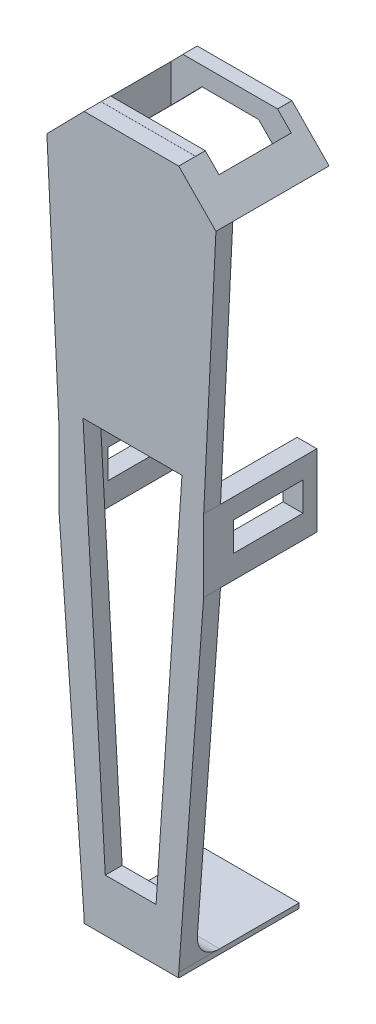
SolidWorks part; units mm, degrees
material "PLA"
ref_plane "Front Plane" through (0, 0, 0) normal (0, 0, 1) x (1, 0, 0)
ref_plane "Top Plane" through (0, 0, 0) normal (0, 1, 0) x (1, 0, 0)
ref_plane "Right Plane" through (0, 0, 0) normal (1, 0, 0) x (0, 0, -1)
sketch "Sketch1" plane through (0, 0, 0) normal (0, 0, 1) x (1, 0, 0)
  line L0 (-37.3414, 34.6091) -> (22.6586, 34.6091)
  line L1 (22.6586, 34.6091) -> (50.9429, 6.3248)
  line L2 (50.9429, 6.3248) -> (50.9429, -53.6752)
  line L3 (50.9429, -53.6752) -> (22.6586, -81.9594)
  line L4 (22.6586, -81.9594) -> (-37.3414, -81.9594)
  line L5 (-37.3414, -81.9594) -> (-64.6578, -54.643)
  line L6 (-64.6578, -54.643) -> (-64.6578, 5.357)
  line L7 (-64.6578, 5.357) -> (-37.3414, 34.6091)
  line L8 (-27.6371, 26.0388) -> (-43.235, 10.1409)
  line L13 (-8.1397, -94.0869) -> (21.8603, -94.0869)
  line L15 (-27.6371, 26.0388) -> (-19.7574, 18.3077)
  line L16 (-43.235, 10.1409) -> (-35.3553, 2.4098)
  line L17 (-19.7574, 18.3077) -> (-35.3553, 2.4098)
  line L18 (-8.1397, 25.9131) -> (-8.1397, 18.1821)
  line L19 (-27.7871, 25.9131) -> (11.5077, 25.9131)
  line L20 (-27.7871, 25.9131) -> (-27.7871, 18.1821)
  line L21 (-27.7871, 18.1821) -> (11.5077, 18.1821)
  line L22 (11.5077, 25.9131) -> (11.5077, 18.1821)
  line L23 (-8.1397, 18.1821) -> (-8.1397, 25.9131) construction
  line L24 (-27.7871, 22.0476) -> (11.5077, 22.0476) construction
  line L25 (26.9557, 10.1409) -> (19.0759, 2.4098)
  line L26 (3.478, 18.3077) -> (19.0759, 2.4098)
  line L27 (11.3577, 26.0388) -> (3.478, 18.3077)
  line L28 (11.3577, 26.0388) -> (26.9557, 10.1409)
  line L29 (21.8603, -94.0869) -> (-38.1397, -94.0869)
  line L30 (21.8603, -94.0869) -> (21.8603, -124.0869)
  line L31 (21.8603, -124.0869) -> (-38.1397, -124.0869)
  line L32 (-38.1397, -94.0869) -> (-38.1397, -124.0869)
  line L33 (-30.3382, -94.0869) -> (13.6618, -94.0869)
  line L34 (-30.3382, -94.0869) -> (-30.3382, -124.0869)
  line L35 (-30.3382, -124.0869) -> (13.6618, -124.0869)
  line L36 (13.6618, -94.0869) -> (13.6618, -124.0869)
  line L37 (-8.3382, -124.0869) -> (-8.3382, -94.0869) construction
  line L38 (-30.3382, -109.0869) -> (13.6618, -109.0869) construction
  point P12 (-8.1397, 22.0476)
  point P17 (-8.3382, -109.0869)
  dimension "D1" = 135
  dimension "D2" = 135
  dimension "D3" = 40
  dimension "D4" = 135
  dimension "D5" = 120
  dimension "D6" = 30
  dimension "D7" = 22.2719
  dimension "D8" = 11.039
  dimension "D9" = 7.7311
  dimension "D10" = 39.2948
  dimension "D11" = 60
  dimension "D12" = 30
  dimension "D13" = 44
extrude "Boss-Extrude1" add sketch "Sketch1" along normal blind 40 contours L21 L20 L8 L16 L17 | L32 L29 L31 | L28 L22 L21 L26 L25 | L29 L36 L31 L30 | L21 L22 L19 L20 region at (-32.4791, 13.2115, 0) region at (16.1997, 13.2115, 0) region at (17.7611, -109.0869, 0) region at (-34.2389, -109.0869, 0)
sketch "Sketch2" plane through (0, 0, 40) normal (0, 0, 1) x (1, 0, 0)
  line L0 (-43.235, 10.1409) -> (-38.1397, -94.0869)
  line L1 (26.9557, 10.1409) -> (21.8603, -94.0869)
  line L2 (-43.235, 10.1409) -> (-27.7871, 25.8859)
  line L3 (-27.7871, 25.8859) -> (11.5077, 25.8859)
  line L4 (11.5077, 25.8859) -> (26.9557, 10.1409)
  line L5 (-27.7871, -264.1141) -> (11.5077, -264.1141)
  line L6 (-38.1397, -94.0869) -> (-38.1397, -124.0869)
  line L7 (-38.1397, -124.0869) -> (-27.7871, -264.1141)
  line L8 (21.8603, -94.0869) -> (21.8603, -124.0869)
  line L9 (21.8603, -124.0869) -> (11.5077, -264.1141)
extrude "Boss-Extrude2" add sketch "Sketch2" along normal blind 7
sketch "Sketch3" plane through (0, -264.1141, 0) normal (0, -1, 0) x (1, 0, 0)
  line L1 (11.5077, 47) -> (-27.7823, 47)
  line L2 (11.5077, 47) -> (11.5077, -3)
  line L3 (11.5077, -3) -> (-27.7823, -3)
  line L4 (-27.7823, 47) -> (-27.7823, -3)
  dimension "D1" = 50
  dimension "D2" = 39.29
extrude "Boss-Extrude3" add sketch "Sketch3" along normal blind 2
fillet "Fillet1" radius 10 1 edges at (-8.1373, -264.1141, 40)
sketch "Sketch4" plane through (-38.1397, 0, 0) normal (-1, 0, 0) x (0, 0, 1)
  line L1 (5.7663, -102.4295) -> (34.6083, -102.4295)
  line L2 (5.7663, -102.4295) -> (5.7663, -114.4295)
  line L3 (5.7663, -114.4295) -> (34.6083, -114.4295)
  line L4 (34.6083, -102.4295) -> (34.6083, -114.4295)
  dimension "D1" = 12
  dimension "D2" = 28.842
extrude "Cut-Extrude1" cut sketch "Sketch4" against normal blind 200
sketch "Sketch5" plane through (0, 25.9131, 0) normal (0, 1, 0) x (1, 0, 0)
  line L1 (-32.8131, -5.9548) -> (17.1869, -5.9548)
  line L2 (-32.8131, -5.9548) -> (-32.8131, -35.9635)
  line L3 (-32.8131, -35.9635) -> (17.1869, -35.9635)
  line L4 (17.1869, -5.9548) -> (17.1869, -35.9635)
  dimension "D1" = 30.0088
  dimension "D2" = 50
extrude "Cut-Extrude2" cut sketch "Sketch5" against normal blind 50
sketch "Sketch6" plane through (0, 0, 47) normal (0, 0, 1) x (1, 0, 0)
  line L0 (-18.9886, -244.3724) -> (2.088, -244.3724)
  line L1 (2.088, -244.3724) -> (12.8541, -84.6492)
  line L2 (12.8541, -84.6492) -> (-28.2376, -84.6492)
  line L3 (-28.2376, -84.6492) -> (-18.9886, -244.3724)
  point P2 (0, 0)
  point P5 (12.8541, -84.6492)
  point P6 (2.088, -244.3724)
extrude "Cut-Extrude3" cut sketch "Sketch6" against normal blind 30
